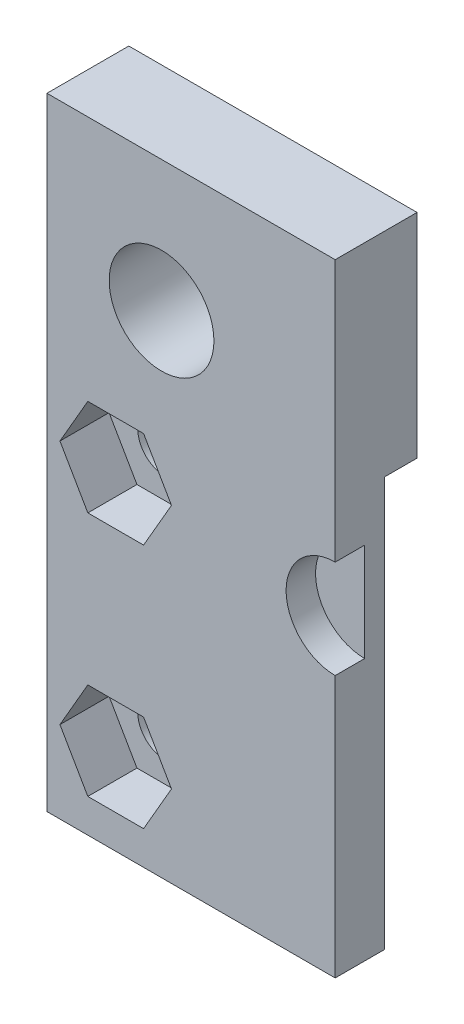
SolidWorks part; units mm, degrees
note: The reader was unsure of these and kept them because the rebuilt part matched: shared geometry of "Sketch4<6>", "Sketch4<7>".
ref_plane "Front Plane" through (0, 0, 0) normal (0, 0, 1) x (1, 0, 0)
ref_plane "Top Plane" through (0, 0, 0) normal (0, 1, 0) x (1, 0, 0)
ref_plane "Right Plane" through (0, 0, 0) normal (1, 0, 0) x (0, 0, -1)
sketch "Sketch1" plane through (0, 0, 0) normal (0, 0, 1) x (1, 0, 0)
  line L0 (-9.4106, 13.8337) -> (-9.4106, -24.1663)
  line L1 (-2.4106, 5.8337) -> (8.196, -4.7729) construction
  line L2 (-9.4106, 13.8337) -> (8.196, 13.8337)
  line L3 (8.196, 13.8337) -> (8.196, -24.1663)
  line L4 (8.196, -24.1663) -> (-9.4106, -24.1663)
  line L6 (-9.4106, 0.8337) -> (8.196, 0.8337) construction
  line L7 (-9.4106, -11.6663) -> (8.196, -11.6663) construction
  circle A0 centre (-2.4106, 5.8337) radius 3.2
  circle A1 centre (-5.2106, -4.1663) radius 1.65
  circle A3 centre (-5.2106, -19.1663) radius 1.65
  point P2 (-2.4106, 5.8337)
  point P3 (8.196, -4.7729)
  point P5 (0, 0)
  dimension "D4" = 8
  dimension "D5" = 5
  dimension "D7" = 6.4
  dimension "D8" = 3.3
  dimension "D1" = 7
  dimension "D3" = 45
  dimension "D6" = 7.5
  dimension "D9" = 5
  dimension "D10" = 5
  dimension "D11" = 4.2
  dimension "D12" = 15
extrude "Boss-Extrude1" add sketch "Sketch1" along normal blind 5
sketch "Sketch4" plane through (0, 0, 5) normal (0, 0, 1) x (1, 0, 0)
  line L7 (-3.5074, -1.2163) -> (-6.9138, -1.2163)
  line L8 (-6.9138, -1.2163) -> (-8.6169, -4.1663)
  line L9 (-8.6169, -4.1663) -> (-6.9138, -7.1163)
  line L10 (-6.9138, -7.1163) -> (-3.5074, -7.1163)
  line L11 (-3.5074, -7.1163) -> (-1.8042, -4.1663)
  line L12 (-1.8042, -4.1663) -> (-3.5074, -1.2163)
  line L13 (8.196, -11.6663) -> (-9.4106, -11.6663) construction
  line L14 (-1.8042, -19.1663) -> (-3.5074, -22.1163)
  line L15 (-3.5074, -16.2163) -> (-1.8042, -19.1663)
  line L16 (-6.9138, -16.2163) -> (-3.5074, -16.2163)
  line L17 (-8.6169, -19.1663) -> (-6.9138, -16.2163)
  line L18 (-6.9138, -22.1163) -> (-8.6169, -19.1663)
  line L19 (-3.5074, -22.1163) -> (-6.9138, -22.1163)
  line L22 (8.196, 0.8337) -> (4.196, 0.8337)
  line L23 (8.196, 0.8337) -> (8.196, -24.1663)
  line L24 (8.196, -24.1663) -> (4.196, -24.1663)
  line L25 (4.196, 0.8337) -> (4.196, -24.1663)
  line L30 (-9.4106, -24.1663) -> (8.196, -24.1663) construction
  line L31 (8.196, -24.1663) -> (8.196, 13.8337) construction
  line L32 (8.196, -2.1663) -> (8.196, -8.1663)
  circle A1 centre (-5.2106, -4.1663) radius 2.95 construction
  arc A2 (8.196, -2.1663) -> (8.196, -8.1663) centre (8.196, -5.1663) ccw
  point P23 (8.196, -4.7729)
  point P28 (4.196, -11.6663)
  dimension "D1" = 5.9
  dimension "D4" = 3
  dimension "D3" = 4
extrude "Cut-Extrude4" cut sketch "Sketch4<6>" along normal blind 2 from surface at -5 contours L22 L25 L24 L23 starting at face at (-3.5606, -4.1663, 0)
sketch "Sketch4<6>" plane through (0, 0, 5) normal (0, 0, 1) x (1, 0, 0) same geometry as "Sketch4"
extrude "Cut-Extrude1" cut sketch "Sketch4" against normal blind 3
extrude "Cut-Extrude5" cut sketch "Sketch4<7>" against normal blind 1.8 contours A2 L32
sketch "Sketch4<7>" plane through (0, 0, 5) normal (0, 0, 1) x (1, 0, 0) same geometry as "Sketch4"
